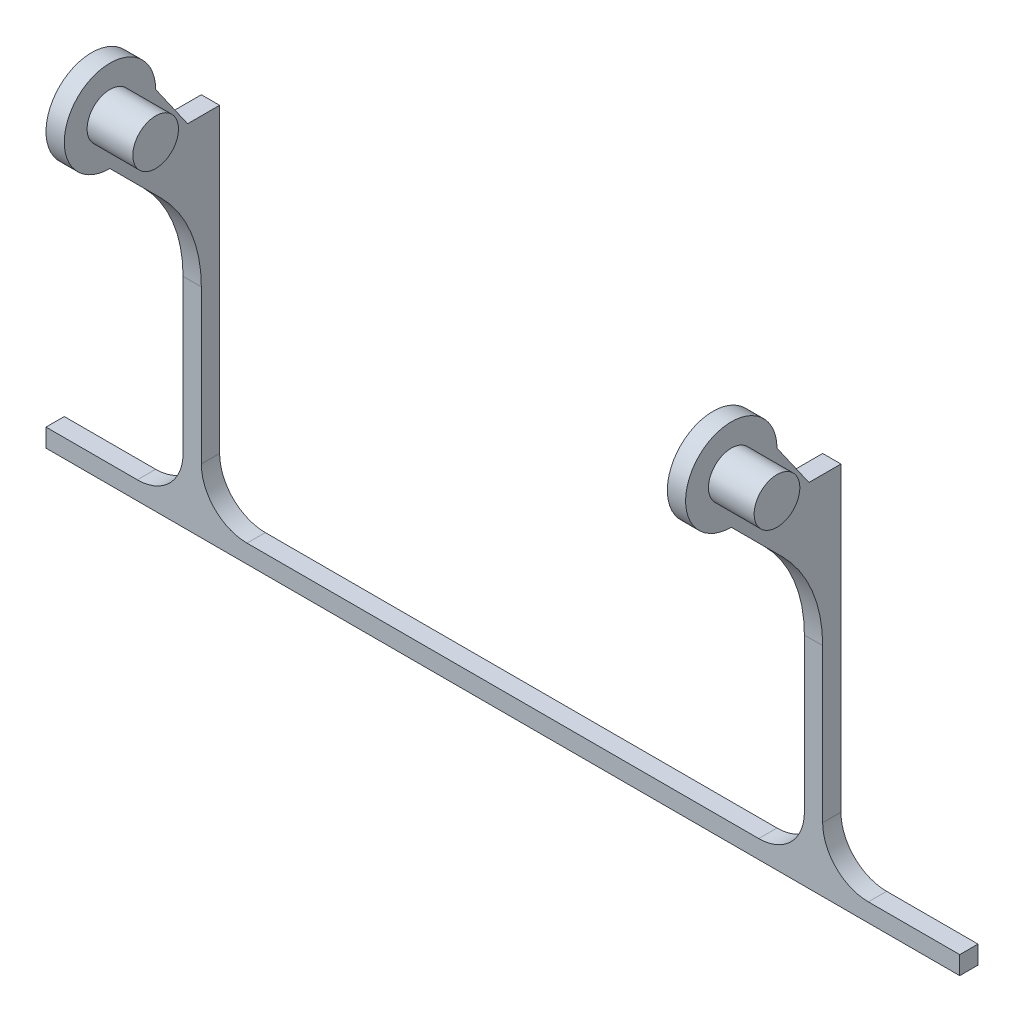
SolidWorks part; units mm, degrees
ref_plane "Plan de face" through (0, 0, 0) normal (0, 0, 1) x (1, 0, 0)
ref_plane "Plan de dessus" through (0, 0, 0) normal (0, 1, 0) x (1, 0, 0)
ref_plane "Plan de droite" through (0, 0, 0) normal (1, 0, 0) x (0, 0, -1)
sketch "Esquisse1" plane through (0, 0, 0) normal (0, 0, 1) x (1, 0, 0)
  line L0 (-100, -100) -> (100, -100) construction
  line L1 (100, -100) -> (100, -180) construction
  line L2 (100, -180) -> (-100, -180) construction
  line L3 (-100, -180) -> (-100, -100) construction
  line L4 (-100, -180) -> (-100, -176) construction
  line L5 (-100, -176) -> (-70, -176) construction
  line L6 (-70, -176) -> (-70, -100) construction
  line L7 (-70, -100) -> (-66, -100) construction
  line L8 (-66, -100) -> (-66, -176) construction
  line L9 (-66, -176) -> (66, -176) construction
  line L10 (66, -176) -> (66, -100) construction
  line L11 (66, -100) -> (70, -100) construction
  line L12 (70, -100) -> (70, -176) construction
  line L13 (70, -176) -> (100, -176) construction
  line L14 (-100, -97.7507) -> (-100, -110) construction
  line L15 (-100, 100) -> (-100, -100) construction
  line L16 (-100, -110) -> (-70, -110) construction
  line L17 (-70, -110) -> (-66, -110) construction
  line L18 (-66, -110) -> (66, -110) construction
  line L19 (66, -110) -> (70, -110) construction
  line L20 (70, -110) -> (100, -110) construction
  line L21 (-70, -110) -> (-66, -110)
  line L22 (-66, -110) -> (-66, -176)
  line L23 (-66, -176) -> (66, -176)
  line L24 (66, -176) -> (66, -110)
  line L25 (66, -110) -> (70, -110)
  line L26 (70, -110) -> (70, -176)
  line L27 (70, -176) -> (100, -176)
  line L28 (100, -176) -> (100, -180)
  line L29 (100, -180) -> (-100, -180)
  line L30 (-100, -180) -> (-100, -176)
  line L31 (-100, -176) -> (-70, -176)
  line L32 (-70, -176) -> (-70, -110)
  dimension "D1" = 4
  dimension "D2" = 4
  dimension "D3" = 4
  dimension "D4" = 4
  dimension "D5" = 4
  dimension "D6" = 30
  dimension "D7" = 30
  dimension "D8" = 10
  dimension "D9" = 80
extrude "Boss.-Extru.1" add sketch "Esquisse1" against normal blind 4
sketch "Esquisse2" plane through (70, 0, 0) normal (1, 0, 0) x (0, 0, -1)
  line L0 (0, -110) -> (-20, -110) construction
  line L1 (-20, -110) -> (-20, -90) construction
  line L2 (4, -110) -> (-10, -90) construction
  line L3 (0, -110) -> (0, -120) construction
  line L4 (0, -176) -> (0, -110) construction
  line L5 (0, -120) -> (-20, -100) construction
  line L6 (0, -120) -> (-20, -100)
  line L7 (4, -110) -> (-10, -90)
  line L8 (0, -120) -> (0, -110)
  line L9 (0, -110) -> (4, -110)
  arc A0 (-10, -90) -> (-20, -100) centre (-20, -90) ccw
  dimension "D3" = 20
  dimension "D1" = 20
  dimension "D2" = 20
  dimension "D4" = 10
extrude "Boss.-Extru.2" add sketch "Esquisse2" against normal blind 4
sketch "Esquisse3" plane through (-70, 0, 0) normal (-1, 0, 0) x (0, 0, 1)
  line L0 (-4, -110) -> (10, -90) construction
  line L1 (20, -100) -> (0, -120) construction
  line L2 (-4, -110) -> (10, -90)
  line L3 (20, -100) -> (0, -120)
  line L4 (-4, -110) -> (0, -110)
  line L5 (0, -110) -> (0, -120)
  arc A0 (20, -100) -> (10, -90) centre (20, -90) ccw construction
  arc A1 (20, -100) -> (10, -90) centre (20, -90) ccw
extrude "Boss.-Extru.3" add sketch "Esquisse3" against normal blind 4
fillet "Congé1" radius 30 2 edges at (68, -120, 0) (-68, -120, 0)
fillet "Congé2" radius 30 2 edges at (-68, -110, -4) (68, -110, -4)
fillet "Congé3" radius 10 4 edges at (66, -176, -2) (-66, -176, -2) (-70, -176, -2) (70, -176, -2)
sketch "Esquisse4" plane through (-70, 0, 0) normal (-1, 0, 0) x (0, 0, 1)
  line L0 (-4, -119.4567) -> (-4, -100)
  line L1 (-4, -100) -> (3, -100)
  line L2 (10, -90) -> (1.423, -102.2528) construction
  line L3 (3, -100) -> (-4, -119.4567)
extrude "Boss.-Extru.4" add sketch "Esquisse4" against normal blind 4
ref_plane "Plan1" through (-66, -100, 3) normal (0, 0, -1) x (-1, 0, 0)
sketch "Esquisse6" plane through (70, 0, 0) normal (1, 0, 0) x (0, 0, -1)
  line L0 (4, -119.4567) -> (4, -100)
  line L1 (4, -100) -> (-3, -100)
  line L2 (-3, -100) -> (4, -119.4567)
extrude "Boss.-Extru.5" add sketch "Esquisse6" against normal blind 4
sketch "Esquisse7" plane through (70, 0, 0) normal (1, 0, 0) x (0, 0, -1)
  line L0 (4, -100) -> (-20, -100) construction
  line L1 (-20, -100) -> (-20, -90) construction
  circle A0 centre (-20, -90) radius 5
  dimension "D1" = 10
extrude "Boss.-Extru.6" add sketch "Esquisse7" along normal blind 10
sketch "Esquisse9" plane through (-70, 0, 0) normal (-1, 0, 0) x (0, 0, 1)
  line L0 (-4, -100) -> (20, -100) construction
  line L1 (20, -100) -> (20, -90) construction
  circle A0 centre (20, -90) radius 5
  dimension "D1" = 10
extrude "Boss.-Extru.7" add sketch "Esquisse9" against normal blind 14
